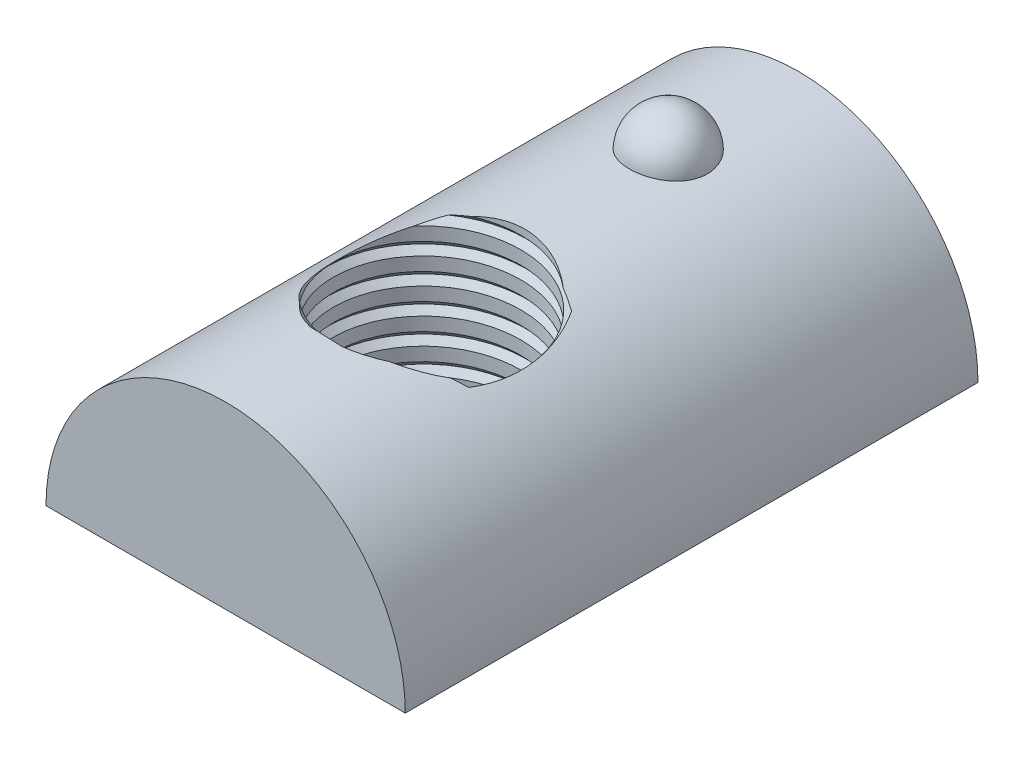
SolidWorks part; units mm, degrees
ref_plane "前视基准面" through (0, 0, 0) normal (0, 0, 1) x (1, 0, 0)
ref_plane "上视基准面" through (0, 0, 0) normal (0, 1, 0) x (1, 0, 0)
ref_plane "右视基准面" through (0, 0, 0) normal (1, 0, 0) x (0, 0, -1)
sketch "草图1" plane through (0, 0, 0) normal (0, 0, 1) x (1, 0, 0)
  line L0 (0, 0) -> (13.8, 0)
  arc A0 (13.8, 0) -> (0, 0) centre (6.9, 0) ccw
  dimension "D1" = 13.8
extrude "凸台-拉伸1" add sketch "草图1" along normal blind 22
sketch "草图2" plane through (0, 0, 0) normal (0, -1, 0) x (1, 0, 0)
  line L0 (0, 22) -> (13.8, 22) construction
  circle A0 centre (6.9, 14.1) radius 3.6
  dimension "D1" = 7.2
  dimension "D2" = 7.9
extrude "切除-拉伸1" cut sketch "草图2" against normal through all
sketch "草图3" plane through (0, 0, 0) normal (0, -1, 0) x (1, 0, 0)
  circle A0 centre (6.9, 14.1) radius 3.6
curve "螺旋线/涡状线1" pitch 1 height 7 radius 3.6 centre (6.9, 0, 14.1) axis (0, 1, 0) start towards (0.7071, 0, 0.7071)
ref_plane "基准面1" through (6.9, 0, 0) normal (1, 0, 0) x (0, 0, -1)
sketch "草图5" plane through (6.9, 0, 0) normal (1, 0, 0) x (0, 0, -1)
  line L0 (-17.7, 1.1168) -> (-17.7, 0.6332)
  line L1 (-17.7, 0.875) -> (-17.9286, 0.875) construction
  line L2 (-17.7, 1.1168) -> (-17.9286, 0.875)
  line L3 (-17.7, 0.6332) -> (-17.9286, 0.875)
sweep "切除-扫描1" cut profiles "草图5" path "螺旋线/涡状线1"
ref_plane "基准面2" through (0, 0, 5) normal (0, 0, -1) x (-1, 0, 0)
sketch "草图7" plane through (0, 0, 5) normal (0, 0, -1) x (-1, 0, 0)
  line L0 (-6.9, 8.2721) -> (-6.9, 5.2721)
  arc A0 (-6.9, 5.2721) -> (-6.9, 8.2721) centre (-6.9, 6.7721) ccw
  dimension "D1" = 3
revolve "旋转6" add sketch "草图7" angle 360 about L0
